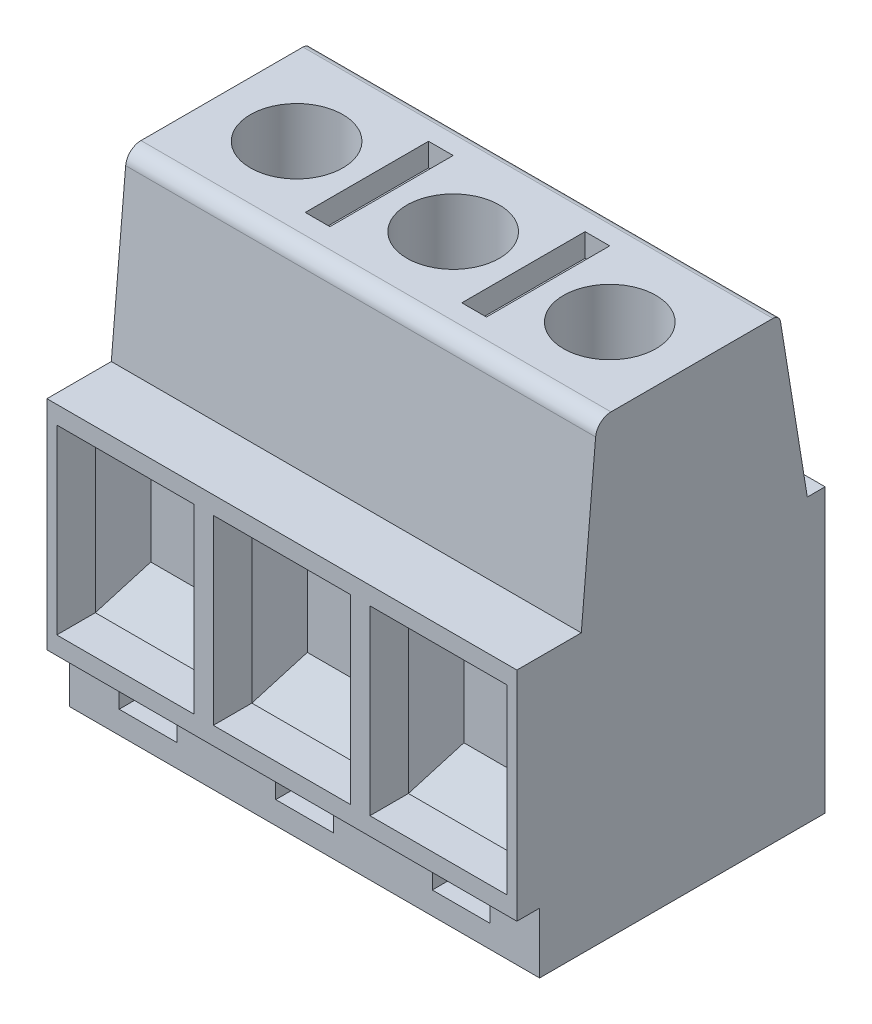
SolidWorks part; units mm, degrees
ref_plane "Front Plane" through (0, 0, 0) normal (0, 0, 1) x (1, 0, 0)
ref_plane "Top Plane" through (0, 0, 0) normal (0, 1, 0) x (1, 0, 0)
ref_plane "Right Plane" through (0, 0, 0) normal (1, 0, 0) x (0, 0, -1)
sketch "Sketch1" plane through (0, 0, 0) normal (1, 0, 0) x (0, 0, -1)
  line L0 (9.6447, 33.3244) -> (29.6447, 33.3244) construction
  line L1 (9.6692, 32.9692) -> (9.6692, 47.0868)
  line L2 (9.6692, 47.0868) -> (13.8475, 47.0868)
  line L3 (13.8475, 47.0868) -> (14.8593, 58.5419)
  line L4 (14.8593, 58.5419) -> (26.709, 58.5419)
  line L5 (26.709, 58.5419) -> (28.5149, 47.3865)
  line L6 (28.5149, 47.3865) -> (29.6692, 47.3865)
  line L7 (29.6692, 47.3865) -> (29.6692, 29.0419)
  line L8 (29.6692, 29.0419) -> (11.1423, 29.0419)
  line L9 (11.1423, 29.0419) -> (11.1423, 32.9692)
  line L10 (11.1423, 32.9692) -> (9.6692, 32.9692)
  line L11 (68.0457, 60.9618) -> (149.3457, 60.9618) construction
  line L12 (139.8559, 49.112) -> (148.7559, 49.112) construction
  line L13 (139.8559, 49.112) -> (139.8559, 37.312) construction
  line L14 (204.1416, 49.112) -> (206.6416, 49.112) construction
  line L15 (208.5587, 45.7504) -> (208.5587, 39.4578) construction
  line L16 (208.5587, 42.6041) -> (206.6416, 42.6041) construction
  line L17 (121.2763, 41.7533) -> (126.7736, 41.7533) construction
  line L18 (217.6919, 61.8593) -> (217.6919, 56.1569) construction
  line L19 (142.8406, 99.3741) -> (145.9297, 99.3741) construction
  line L20 (211.5813, 61.8593) -> (211.5813, 60.3558) construction
  line L21 (118.1896, 87.8673) -> (119.7969, 87.8673) construction
  line L22 (118.1896, 87.8673) -> (118.1896, 95.8627) construction
  line L23 (118.1896, 95.8627) -> (119.7969, 95.8627) construction
  line L24 (119.7969, 87.8673) -> (119.7969, 95.8627) construction
  line L25 (170.4098, 32.3653) -> (173.8098, 32.3653) construction
  line L26 (173.8098, 32.3653) -> (175.1098, 32.3653) construction
  line L27 (175.1098, 32.3653) -> (178.3098, 32.3653) construction
  line L28 (178.3098, 32.3653) -> (179.6098, 32.3653) construction
  line L29 (179.6098, 32.3653) -> (183.0098, 32.3653) construction
  line L30 (183.0098, 32.3653) -> (184.3098, 32.3653) construction
  line L31 (142.4541, 34.5696) -> (146.1866, 34.5696) construction
  line L32 (146.1866, 34.5696) -> (142.4541, 34.5696) construction
  line L33 (142.4541, 34.5696) -> (142.4541, 33.584) construction
  circle A0 centre (134.2519, 91.3377) radius 3.0186 construction
  dimension "D1" = 20
  dimension "D2" = 20
  dimension "D3" = 29.5
  dimension "D4" = 9.6692
  dimension "D5" = 11.1423
  dimension "D6" = 13.8475
  dimension "D7" = 14.8593
  dimension "D8" = 26.709
  dimension "D9" = 28.5149
  dimension "D10" = 29.0419
  dimension "D11" = 32.9692
  dimension "D12" = 33.3244
  dimension "D13" = 47.0868
  dimension "D14" = 47.3865
  dimension "D15" = 81.3
  dimension "D16" = 8.9
  dimension "D17" = 11.8
  dimension "D18" = 2.5
  dimension "D19" = 1.6073
  dimension "D20" = 7.9954
  dimension "D21" = 3.4
  dimension "D22" = 1.3
  dimension "D23" = 3.2
  dimension "D24" = 1.3
  dimension "D25" = 3.4
  dimension "D26" = 1.3
extrude "Boss-Extrude1" add sketch "Sketch1" along normal blind 10.16
sketch "Sketch2" plane through (0, 0, -9.6692) normal (0, 0, 1) x (1, 0, 0)
  line L0 (0, 47.0868) -> (0, 32.9692) construction
  line L1 (0.63, 34.128) -> (9.53, 34.128)
  line L2 (0.63, 34.128) -> (0.63, 45.928)
  line L3 (0.63, 45.928) -> (9.53, 45.928)
  line L4 (9.53, 34.128) -> (9.53, 45.928)
  line L5 (0.63, 34.128) -> (9.53, 45.928) construction
  line L6 (0.63, 45.928) -> (9.53, 34.128) construction
  line L7 (10.16, 47.0868) -> (0, 47.0868) construction
  point P0 (5.08, 40.028)
  point P5 (0, 0)
  point P8 (0, 40.028)
  point P9 (0, 0)
  point P12 (5.08, 47.0868)
  point P13 (9.3089, 45.6013)
  dimension "D1" = 8.9
  dimension "D2" = 11.8
extrude "Cut-Extrude1" cut sketch "Sketch2" against normal blind 2.5
sketch "Sketch3" plane through (0, 0, -12.1692) normal (0, 0, 1) x (1, 0, 0)
  line L4 (9.53, 34.128) -> (9.53, 45.928)
  line L5 (9.53, 45.928) -> (0.63, 45.928)
  line L6 (0.63, 45.928) -> (0.63, 34.128)
  line L7 (0.63, 34.128) -> (9.53, 34.128)
  line L8 (9.53, 34.128) -> (9.53, 45.928)
  line L9 (9.53, 45.928) -> (0.63, 45.928)
  line L10 (0.63, 45.928) -> (0.63, 34.128)
  line L11 (0.63, 34.128) -> (9.53, 34.128)
  dimension "D1" = 0
ref_plane "Plane1" through (0, 0, -14.0692) normal (0, 0, 1) x (1, 0, 0)
sketch "Sketch4" plane through (0, 0, -14.0692) normal (0, 0, 1) x (1, 0, 0)
  line L0 (9.53, 45.928) -> (0.63, 45.928) construction
  line L1 (2.33, 36.878) -> (7.83, 36.878)
  line L2 (2.33, 36.878) -> (2.33, 43.178)
  line L3 (2.33, 43.178) -> (7.83, 43.178)
  line L4 (7.83, 36.878) -> (7.83, 43.178)
  line L5 (2.33, 36.878) -> (7.83, 43.178) construction
  line L6 (2.33, 43.178) -> (7.83, 36.878) construction
  line L7 (0.63, 45.928) -> (0.63, 34.128) construction
  point P0 (5.08, 40.028)
  point P5 (0, 0)
  point P8 (5.08, 45.928)
  point P9 (0, 0)
  point P12 (0.63, 40.028)
  dimension "D1" = 6.3
  dimension "D2" = 5.5
loft "Cut-Loft1" cut profiles "Sketch3", "Sketch4" connector at (0.63, 45.928, -12.1692) connector at (2.33, 43.178, -14.0692)
sketch "Sketch5" plane through (0, 58.5419, 0) normal (0, 1, 0) x (1, 0, 0)
  line L0 (10.16, 26.709) -> (10.16, 14.8593) construction
  line L1 (10.16, 29.6692) -> (0, 29.6692) construction
  circle A0 centre (5.08, 20.7842) radius 3
  point P2 (0, 0)
  point P5 (10.16, 20.7842)
  point P6 (0, 0)
  point P9 (5.08, 29.6692)
  dimension "D1" = 6
extrude "Cut-Extrude2" cut sketch "Sketch5" against normal blind 5.7
sketch "Sketch7" plane through (0, 29.0419, 0) normal (0, -1, 0) x (1, 0, 0)
  line L0 (10.16, -11.1423) -> (0, -11.1423) construction
  line L1 (4.43, -27.5692) -> (5.73, -27.5692)
  line L2 (4.43, -27.5692) -> (4.43, -26.7692)
  line L3 (4.43, -26.7692) -> (5.73, -26.7692)
  line L4 (5.73, -27.5692) -> (5.73, -26.7692)
  line L5 (4.43, -27.5692) -> (5.73, -26.7692) construction
  line L6 (4.43, -26.7692) -> (5.73, -27.5692) construction
  line L7 (4.43, -17.4092) -> (5.73, -17.4092)
  line L8 (4.43, -17.4092) -> (4.43, -16.6092)
  line L9 (4.43, -16.6092) -> (5.73, -16.6092)
  line L10 (5.73, -17.4092) -> (5.73, -16.6092)
  line L11 (4.43, -17.4092) -> (5.73, -16.6092) construction
  line L12 (4.43, -16.6092) -> (5.73, -17.4092) construction
  line L13 (10.16, -29.6692) -> (0, -29.6692) construction
  point P0 (5.08, -27.1692)
  point P5 (5.08, -17.0092)
  point P10 (0, 0)
  point P13 (5.08, -11.1423)
  dimension "D1" = 1.3
  dimension "D2" = 0.8
  dimension "D3" = 2.5
  dimension "D4" = 10.16
extrude "Boss-Extrude2" add sketch "Sketch7" along normal blind 4.5
sketch "Sketch8" plane through (0, 0, -16.6092) normal (0, 0, 1) x (1, 0, 0)
  line L0 (4.43, 24.5419) -> (4.43, 29.0419) construction
  line L1 (5.73, 24.5419) -> (5.73, 29.0419) construction
  line L2 (5.73, 24.5419) -> (4.43, 24.5419) construction
  arc A0 (4.43, 25.1919) -> (5.73, 25.1919) centre (5.08, 25.1919) ccw
  point P3 (5.08, 24.5419)
extrude "Cut-Extrude5" cut sketch "Sketch8" against normal through all flip side to cut
ref_plane "Plane2" through (0, 38.5279, -38.5279) normal (0, 0.7071, -0.7071) x (-1, 0, 0)
sketch "Sketch10" plane through (0, 38.5279, -38.5279) normal (0, 0.7071, -0.7071) x (-1, 0, 0)
  line L0 (-10.16, 12.528) -> (0, 12.528) construction
  circle A0 centre (-5.08, 12.528) radius 1.5
  dimension "D1" = 3
extrude "Cut-Extrude6" cut sketch "Sketch10" against normal blind 4.5 contours A0
sketch "Sketch13" plane through (0, 0, -11.1423) normal (0, 0, 1) x (1, 0, 0)
  line L0 (10.16, 32.9692) -> (10.16, 29.0419) construction
  line L1 (3.205, 30.5055) -> (6.955, 30.5055)
  line L2 (3.205, 30.5055) -> (3.205, 31.5055)
  line L3 (3.205, 31.5055) -> (6.955, 31.5055)
  line L4 (6.955, 30.5055) -> (6.955, 31.5055)
  line L5 (3.205, 30.5055) -> (6.955, 31.5055) construction
  line L6 (3.205, 31.5055) -> (6.955, 30.5055) construction
  line L7 (10.16, 32.9692) -> (0, 32.9692) construction
  point P0 (5.08, 31.0055)
  point P5 (0, 0)
  point P8 (10.16, 31.0055)
  point P9 (0, 0)
  point P12 (5.08, 32.9692)
  dimension "D1" = 3.75
  dimension "D2" = 1
extrude "Cut-Extrude8" cut sketch "Sketch13" against normal blind 3
fillet "Fillet3" radius 0.5 1 edges at (5.08, 58.5419, -26.709) type face fillet first side face at (5.08, 58.5419, -17.7842) second side face at (5.08, 51.2437, -27.8905)
fillet "Fillet4" radius 1 1 edges at (5.08, 58.5419, -14.8593) type face fillet first side face at (5.08, 58.5419, -17.7842) second side face at (5.08, 52.8143, -14.3534)
sketch "Sketch12" plane through (0, 29.0419, 0) normal (0, -1, 0) x (1, 0, 0)
  line L1 (-0.65, -15.8423) -> (0.65, -15.8423)
  line L2 (-0.65, -15.8423) -> (-0.65, -14.5423)
  line L3 (-0.65, -14.5423) -> (0.65, -14.5423)
  line L4 (0.65, -15.8423) -> (0.65, -14.5423)
  line L5 (-0.65, -15.8423) -> (0.65, -14.5423) construction
  line L6 (-0.65, -14.5423) -> (0.65, -15.8423) construction
  line L8 (-0.65, -20.3423) -> (0.65, -20.3423)
  line L9 (-0.65, -20.3423) -> (-0.65, -19.0423)
  line L10 (-0.65, -19.0423) -> (0.65, -19.0423)
  line L11 (0.65, -20.3423) -> (0.65, -19.0423)
  line L12 (-0.65, -20.3423) -> (0.65, -19.0423) construction
  line L13 (-0.65, -19.0423) -> (0.65, -20.3423) construction
  line L14 (-0.65, -25.0423) -> (0.65, -25.0423)
  line L15 (-0.65, -25.0423) -> (-0.65, -23.7423)
  line L16 (-0.65, -23.7423) -> (0.65, -23.7423)
  line L17 (0.65, -25.0423) -> (0.65, -23.7423)
  line L18 (-0.65, -25.0423) -> (0.65, -23.7423) construction
  line L19 (-0.65, -23.7423) -> (0.65, -25.0423) construction
  line L20 (10.16, -11.1423) -> (0, -11.1423) construction
  line L21 (0, -11.1423) -> (0, -29.6692) construction
  point P0 (0, -15.1923)
  point P5 (0, 0)
  point P6 (0, -15.1923)
  point P7 (0, -19.6923)
  point P12 (0, -24.3923)
  point P21 (0, 0)
  point P22 (0, 0)
  point P23 (0, -15.1923)
  point P24 (0, -19.6923)
  point P25 (0, -24.3923)
  dimension "D1" = 3.4
  dimension "D2" = 1.3
  dimension "D3" = 3.2
  dimension "D4" = 3.4
  dimension "D5" = 1.3
extrude "Boss-Extrude3" add sketch "Sketch12" along normal blind 0.5 separate body
sketch "Sketch14" plane through (10.16, 0, 0) normal (1, 0, 0) x (0, 0, -1)
  line L10 (26.2835, 58.5419) -> (15.7749, 58.5419)
  line L11 (14.7788, 57.6298) -> (13.8475, 47.0868)
  line L12 (13.8475, 47.0868) -> (9.6692, 47.0868)
  line L13 (9.6692, 47.0868) -> (9.6692, 32.9692)
  line L14 (9.6692, 32.9692) -> (11.1423, 32.9692)
  line L15 (11.1423, 32.9692) -> (11.1423, 29.0419)
  line L16 (11.1423, 29.0419) -> (29.6692, 29.0419)
  line L17 (29.6692, 29.0419) -> (29.6692, 47.3865)
  line L18 (29.6692, 47.3865) -> (28.5149, 47.3865)
  line L19 (28.5149, 47.3865) -> (26.777, 58.1218)
  line L21 (14.7788, 57.6298) -> (13.8475, 47.0868)
  line L22 (13.8475, 47.0868) -> (9.6692, 47.0868)
  line L23 (9.6692, 47.0868) -> (9.6692, 32.9692)
  line L24 (9.6692, 32.9692) -> (11.1423, 32.9692)
  line L25 (11.1423, 32.9692) -> (11.1423, 29.0419)
  line L26 (11.1423, 29.0419) -> (29.6692, 29.0419)
  line L27 (29.6692, 29.0419) -> (29.6692, 47.3865)
  line L28 (29.6692, 47.3865) -> (28.5149, 47.3865)
  line L29 (28.5149, 47.3865) -> (26.777, 58.1218)
  line L31 (26.2835, 58.5419) -> (15.7749, 58.5419)
  arc A3 (26.777, 58.1218) -> (26.2835, 58.5419) centre (26.2835, 58.0419) ccw
  arc A6 (26.777, 58.1218) -> (26.2835, 58.5419) centre (26.2835, 58.0419) ccw
  arc A8 (15.7749, 58.5419) -> (14.7788, 57.6298) centre (15.7749, 57.5419) ccw
  arc A9 (15.7749, 58.5419) -> (14.7788, 57.6298) centre (15.7749, 57.5419) ccw
  dimension "D1" = 0
extrude "Boss-Extrude4" add sketch "Sketch14" along normal blind 0.01
ref_plane "Plane3" through (0, 0, 0) normal (-1, 0, 0) x (0, 0, 1)
pattern_linear "LPattern8" count 3 spacing 10.16 along (-1, 0, 0) of "Boss-Extrude1", "Cut-Extrude1", "Cut-Loft1", "Cut-Extrude2", "Boss-Extrude2", "Cut-Extrude5", "Cut-Extrude6", "Cut-Extrude8", "Fillet3", "Fillet4"
sketch "Sketch11" plane through (0, 58.5419, 0) normal (0, 1, 0) x (1, 0, 0)
  line L1 (-0.8, 17.0641) -> (0.8, 17.0641)
  line L2 (-0.8, 17.0641) -> (-0.8, 25.0641)
  line L3 (-0.8, 25.0641) -> (0.8, 25.0641)
  line L4 (0.8, 17.0641) -> (0.8, 25.0641)
  line L5 (-0.8, 17.0641) -> (0.8, 25.0641) construction
  line L6 (-0.8, 25.0641) -> (0.8, 17.0641) construction
  line L8 (0, 55) -> (0, -55) construction
  point P0 (0, 21.0641)
  point P5 (1.8522, 20.6032)
  point P6 (1.6707, 20.773)
  point P7 (0, 0)
  point P8 (0, 0)
  point P12 (0, 0)
  point P13 (0.3317, 21.0641)
  point P16 (0, 0)
  dimension "D1" = 1.6
  dimension "D2" = 8
extrude "Cut-Extrude7" cut sketch "Sketch11" against normal blind 1.5
pattern_linear "LPattern9" count 2 spacing 10.16 along (-1, 0, 0) of "Boss-Extrude3", "Cut-Extrude7"
sketch "Sketch16" plane through (-20.32, 0, 0) normal (-1, 0, 0) x (0, 0, 1)
  line L10 (-13.8475, 47.0868) -> (-14.7788, 57.6298)
  line L11 (-15.7749, 58.5419) -> (-26.2835, 58.5419)
  line L12 (-26.777, 58.1218) -> (-28.5149, 47.3865)
  line L13 (-28.5149, 47.3865) -> (-29.6692, 47.3865)
  line L14 (-29.6692, 47.3865) -> (-29.6692, 29.0419)
  line L15 (-29.6692, 29.0419) -> (-11.1423, 29.0419)
  line L16 (-11.1423, 29.0419) -> (-11.1423, 32.9692)
  line L17 (-11.1423, 32.9692) -> (-9.6692, 32.9692)
  line L18 (-9.6692, 32.9692) -> (-9.6692, 47.0868)
  line L19 (-9.6692, 47.0868) -> (-13.8475, 47.0868)
  line L42 (-13.8475, 47.0868) -> (-14.7788, 57.6298)
  line L43 (-15.7749, 58.5419) -> (-26.2835, 58.5419)
  line L44 (-26.777, 58.1218) -> (-28.5149, 47.3865)
  line L45 (-28.5149, 47.3865) -> (-29.6692, 47.3865)
  line L46 (-29.6692, 47.3865) -> (-29.6692, 29.0419)
  line L47 (-29.6692, 29.0419) -> (-11.1423, 29.0419)
  line L48 (-11.1423, 29.0419) -> (-11.1423, 32.9692)
  line L49 (-11.1423, 32.9692) -> (-9.6692, 32.9692)
  line L50 (-9.6692, 32.9692) -> (-9.6692, 47.0868)
  line L51 (-9.6692, 47.0868) -> (-13.8475, 47.0868)
  arc A2 (-14.7788, 57.6298) -> (-15.7749, 58.5419) centre (-15.7749, 57.5419) ccw
  arc A8 (-26.2835, 58.5419) -> (-26.777, 58.1218) centre (-26.2835, 58.0419) ccw
  arc A10 (-14.7788, 57.6298) -> (-15.7749, 58.5419) centre (-15.7749, 57.5419) ccw
  arc A11 (-26.2835, 58.5419) -> (-26.777, 58.1218) centre (-26.2835, 58.0419) ccw
  dimension "D1" = 0
extrude "Boss-Extrude6" add sketch "Sketch16" along normal blind 0.01
